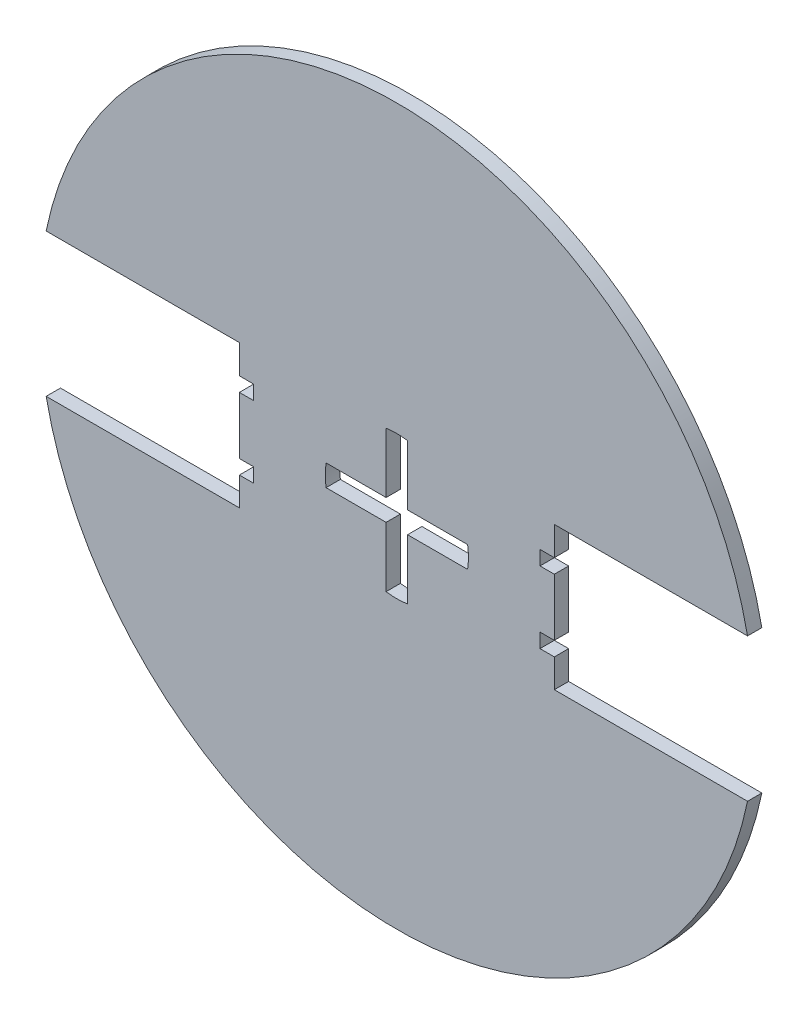
SolidWorks part; units mm, degrees
note: The reader was unsure of these and kept them because the rebuilt part matched: shared geometry of "Sketch11<3>", "Sketch1<9>".
ref_plane "Front Plane" through (0, 0, 0) normal (0, 0, 1) x (1, 0, 0)
ref_plane "Top Plane" through (0, 0, 0) normal (0, 1, 0) x (1, 0, 0)
ref_plane "Right Plane" through (0, 0, 0) normal (1, 0, 0) x (0, 0, -1)
sketch "Sketch1" plane through (0, 0, 0) normal (0, 0, 1) x (1, 0, 0)
  line L0 (0, 0) -> (-40, 0)
  line L1 (0, 0) -> (20, 0)
  line L2 (-10, 0) -> (-10, 10)
  line L3 (-44.5, 2) -> (-35.5, 2)
  line L4 (-44.5, 2) -> (-44.5, -2)
  line L5 (-44.5, -2) -> (-35.5, -2)
  line L6 (-35.5, 2) -> (-35.5, -2)
  line L7 (-44.5, 2) -> (-35.5, -2) construction
  line L8 (-44.5, -2) -> (-35.5, 2) construction
  line L9 (-10, 10) -> (-48.9898, 10)
  line L10 (-10, 0) -> (-10, -10)
  line L11 (-10, -10) -> (-48.9898, -10)
  line L12 (-10, 10) -> (-32.4949, 10)
  line L13 (-10, 10) -> (-16, 10)
  line L14 (10, 0) -> (10, 10)
  line L15 (10, 10) -> (48.9898, 10)
  line L16 (10, 0) -> (10, -10)
  line L17 (10, -10) -> (48.9898, -10)
  line L18 (10, 10) -> (32.4949, 10)
  line L19 (10, 10) -> (22, 10)
  line L20 (22, 10) -> (22, -10)
  line L21 (-10, 10) -> (-22, 10)
  line L22 (-22, 10) -> (-22, -10)
  circle A0 centre (0, 0) radius 50
  circle A1 centre (0, 0) radius 10
  circle A2 centre (0, 0) radius 50
  dimension "D1" = 100
  dimension "D5" = 20
  dimension "D2" = 4
  dimension "D3" = 9
  dimension "D4" = 40
extrude "Boss-Extrude5" add sketch "Sketch1" against normal blind 2
sketch "Sketch11" plane through (0, 0, -2) normal (0, 0, -1) x (-1, 0, 0)
  line L1 (1.5, -1.5) -> (-1.5, -1.5)
  line L2 (1.5, -1.5) -> (1.5, 1.5)
  line L3 (1.5, 1.5) -> (-1.5, 1.5)
  line L4 (-1.5, -1.5) -> (-1.5, 1.5)
  line L5 (1.5, -1.5) -> (-1.5, 1.5) construction
  line L6 (-1.5, 1.5) -> (-9.8869, 1.5)
  line L7 (-1.5, -1.5) -> (-9.8869, -1.5)
  line L8 (1.5, 1.5) -> (9.8869, 1.5)
  line L9 (1.5, -1.5) -> (9.8869, -1.5)
  line L10 (1.5, 1.5) -> (1.5, 9.8869)
  line L11 (-1.5, 1.5) -> (-1.5, 9.8869)
  line L12 (-1.5, -1.5) -> (-1.5, -9.8869)
  line L13 (1.5, -1.5) -> (1.5, -9.8869)
  line L14 (1.5, 1.5) -> (-1.5, -1.5) construction
  circle A0 centre (0, 0) radius 10
  dimension "D1" = 20
  dimension "D2" = 3
extrude "Cut-Extrude17" cut sketch "Sketch11" against normal blind 2 contours L10 A0 L11 L6 L7 L12 L13 L9 L8
extrude "Cut-Extrude18" cut sketch "Sketch11<3>" against normal blind 2 contours L6 A0 L7 L4 | L9 A0 L8 L2 | L12 A0 L13 L1 | L4 L1 L2 L3
sketch "Sketch11<3>" plane through (0, 0, -2) normal (0, 0, -1) x (-1, 0, 0) same geometry as "Sketch11"
extrude "Cut-Extrude19" cut sketch "Sketch1<9>" against normal blind 2 contours L17 A0 L15 L18 L20
sketch "Sketch1<9>" plane through (0, 0, 0) normal (0, 0, 1) x (1, 0, 0) same geometry as "Sketch1"
ref_plane "Plane2" through (22, 0, 0) normal (1, 0, 0) x (0, 0, -1)
sketch "Sketch13" plane through (22, 0, 0) normal (1, 0, 0) x (0, 0, -1)
  line L0 (0, 10) -> (1.9985, 10)
  line L1 (2, 10) -> (0, 10) construction
  line L2 (2, 10) -> (0, 10) construction
  line L3 (0.9993, 10) -> (0.9993, 4.9728)
  line L4 (0, -10) -> (1.9985, -10)
  line L5 (2, -10) -> (0, -10) construction
  line L6 (2, -10) -> (0, -10) construction
  line L7 (0.9993, -10) -> (0.9993, -5.0281)
  line L8 (2, 10) -> (2, -10) construction
  line L9 (-0.0015, -4.0281) -> (2, -4.0281)
  line L10 (-0.0015, -4.0281) -> (-0.0015, -6.0281)
  line L11 (-0.0015, -6.0281) -> (2, -6.0281)
  line L12 (2, -4.0281) -> (2, -6.0281)
  line L13 (-0.0015, -4.0281) -> (2, -6.0281) construction
  line L14 (-0.0015, -6.0281) -> (2, -4.0281) construction
  line L16 (-0.0015, 5.9728) -> (2, 5.9728)
  line L17 (-0.0015, 5.9728) -> (-0.0015, 3.9728)
  line L18 (-0.0015, 3.9728) -> (2, 3.9728)
  line L19 (2, 5.9728) -> (2, 3.9728)
  line L20 (-0.0015, 5.9728) -> (2, 3.9728) construction
  line L21 (-0.0015, 3.9728) -> (2, 5.9728) construction
  dimension "D1" = 2
  dimension "D2" = 2
ref_plane "Plane3" through (-22, 0, 0) normal (-1, 0, 0) x (0, 0, 1)
sketch "Sketch14" plane through (-22, 0, 0) normal (-1, 0, 0) x (0, 0, 1)
  line L0 (-2, 10) -> (0, 10)
  line L1 (-0.9993, 10) -> (-0.9993, 4.9728)
  line L2 (-0.9993, -10) -> (-0.9993, -5.0281)
  line L4 (-2, -4.0281) -> (0.0015, -4.0281)
  line L5 (-2, -4.0281) -> (-2, -6.0281)
  line L6 (-2, -6.0281) -> (0.0015, -6.0281)
  line L7 (0.0015, -4.0281) -> (0.0015, -6.0281)
  line L8 (-2, -4.0281) -> (0.0015, -6.0281) construction
  line L9 (-2, -6.0281) -> (0.0015, -4.0281) construction
  line L10 (-2, 5.9728) -> (0.0015, 5.9728)
  line L11 (-2, 5.9728) -> (-2, 3.9728)
  line L12 (-2, 3.9728) -> (0.0015, 3.9728)
  line L13 (0.0015, 5.9728) -> (0.0015, 3.9728)
  line L14 (-2, 5.9728) -> (0.0015, 3.9728) construction
  line L15 (-2, 3.9728) -> (0.0015, 5.9728) construction
extrude "Cut-Extrude20" cut sketch "Sketch14" against normal blind 2
extrude "Cut-Extrude21" cut sketch "Sketch13" against normal blind 2
